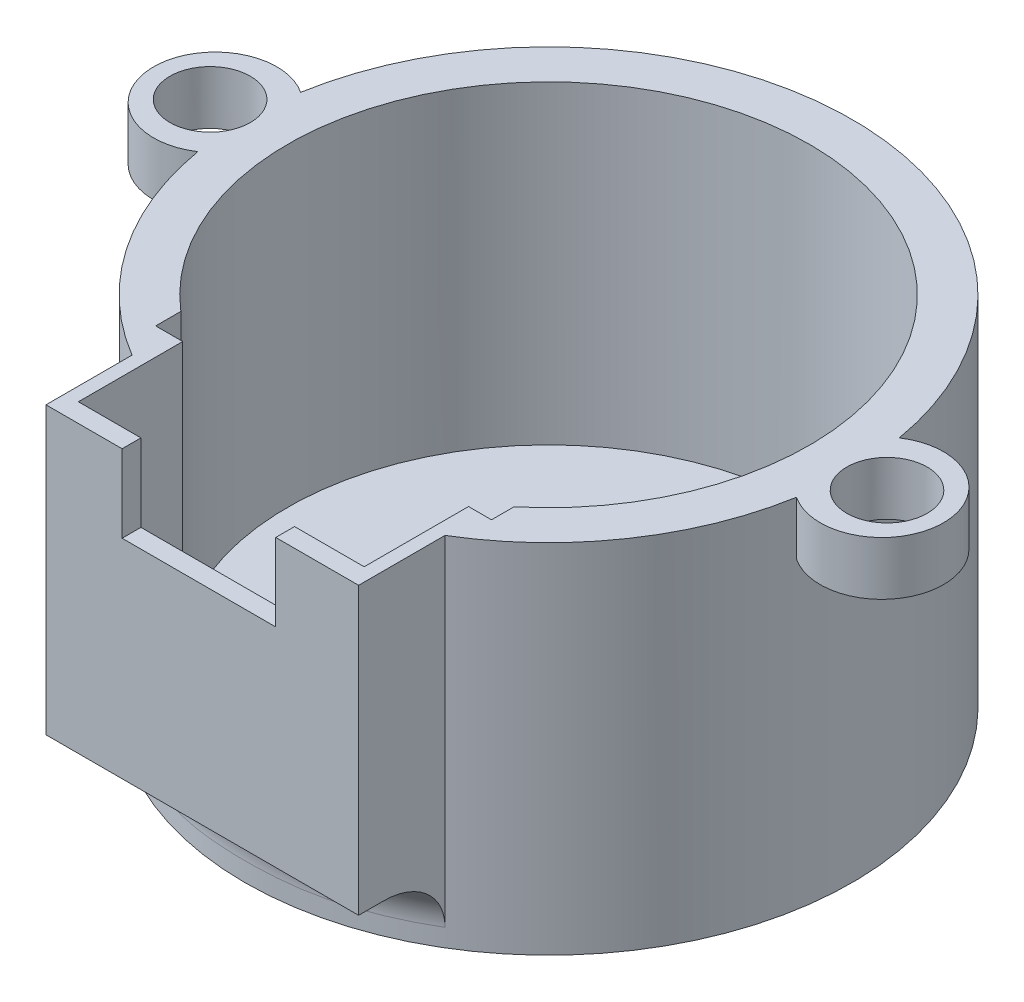
SolidWorks part; units mm, degrees
ref_plane "Front Plane" through (0, 0, 0) normal (0, 0, 1) x (1, 0, 0)
ref_plane "Top Plane" through (0, 0, 0) normal (0, 1, 0) x (1, 0, 0)
ref_plane "Right Plane" through (0, 0, 0) normal (1, 0, 0) x (0, 0, -1)
sketch "Sketch1" plane through (0, 0, 0) normal (0, 1, 0) x (1, 0, 0)
  circle A0 centre (0, 0) radius 17
  dimension "D1" = 34
extrude "Boss-Extrude1" add sketch "Sketch1" along normal blind 20
shell "Shell1" thickness 2.4 removed face at (0, 20, 17)
sketch "Sketch2" plane through (0, 20, 0) normal (0, 1, 0) x (1, 0, 0)
  line L0 (-14.6, 0) -> (37.717, 0) construction
  line L1 (0, 0) -> (0, -36.0151) construction
  circle A0 centre (0, 0) radius 14.6 construction
  circle A3 centre (18.6594, 0) radius 3.45
  circle A4 centre (-18.6594, 0) radius 3.45
extrude "Boss-Extrude3" add sketch "Sketch2" against normal blind 3
sketch "Sketch4" plane through (0, 20, 0) normal (0, 1, 0) x (1, 0, 0)
  line L0 (0, 0) -> (0, -29.7272) construction
  circle A0 centre (18.9465, 0) radius 2.25
  circle A1 centre (-18.9465, 0) radius 2.25
  dimension "D1" = 4.5
extrude "Cut-Extrude1" cut sketch "Sketch4" against normal blind 3
sketch "Sketch5" plane through (0, 20, 0) normal (0, 1, 0) x (1, 0, 0)
  line L1 (-8.7324, -11.7006) -> (8.7676, -11.7006)
  line L2 (-8.7324, -11.7006) -> (-8.7324, -19.4006)
  line L3 (-8.7324, -19.4006) -> (8.7676, -19.4006)
  line L4 (8.7676, -11.7006) -> (8.7676, -19.4006)
  circle A0 centre (0, 0) radius 14.6 construction
  point P6 (-8.5925, -11.8037)
  point P7 (-8.7324, -11.7006)
  dimension "D1" = 17.5
  dimension "D2" = 7.7
extrude "Boss-Extrude4" add sketch "Sketch5" against normal blind 16
sketch "Sketch6" plane through (0, 20, 0) normal (0, 1, 0) x (1, 0, 0)
  line L1 (-7.974, -18.3476) -> (8.026, -18.3476)
  line L2 (-7.974, -18.3476) -> (-7.974, -9.7476)
  line L3 (-7.974, -9.7476) -> (8.026, -9.7476)
  line L4 (8.026, -18.3476) -> (8.026, -9.7476)
  point P4 (5.5075, -9.6713)
  point P5 (8.026, -9.7476)
  dimension "D1" = 16
  dimension "D2" = 8.6
extrude "Cut-Extrude2" cut sketch "Sketch6" against normal blind 14
sketch "Sketch7" plane through (0, 0, 19.4006) normal (0, 0, 1) x (1, 0, 0)
  line L1 (-4.4725, 15.661) -> (4.1275, 15.661)
  line L2 (-4.4725, 15.661) -> (-4.4725, 21.461)
  line L3 (-4.4725, 21.461) -> (4.1275, 21.461)
  line L4 (4.1275, 15.661) -> (4.1275, 21.461)
  dimension "D1" = 8.6
  dimension "D2" = 5.8
extrude "Cut-Extrude3" cut sketch "Sketch7" against normal blind 5
fillet "Fillet3" radius 3 1 edges at (0.0205, 4, 17)
fillet "Fillet4" radius 1 1 edges at (0, 4, 11.7006)
sketch "Sketch8" plane through (0, 20, 0) normal (0, 1, 0) x (1, 0, 0)
  line L1 (-9.4877, -12.5059) -> (9.3123, -12.5059)
  line L2 (-9.4877, -12.5059) -> (-9.4877, -10.1059)
  line L3 (-9.4877, -10.1059) -> (9.3123, -10.1059)
  line L4 (9.3123, -12.5059) -> (9.3123, -10.1059)
  point P4 (-9.7215, -12.4096)
  point P5 (9.3123, -12.5059)
  dimension "D1" = 18.8
  dimension "D2" = 2.4
extrude "Cut-Extrude4" cut sketch "Sketch8" against normal blind 16
